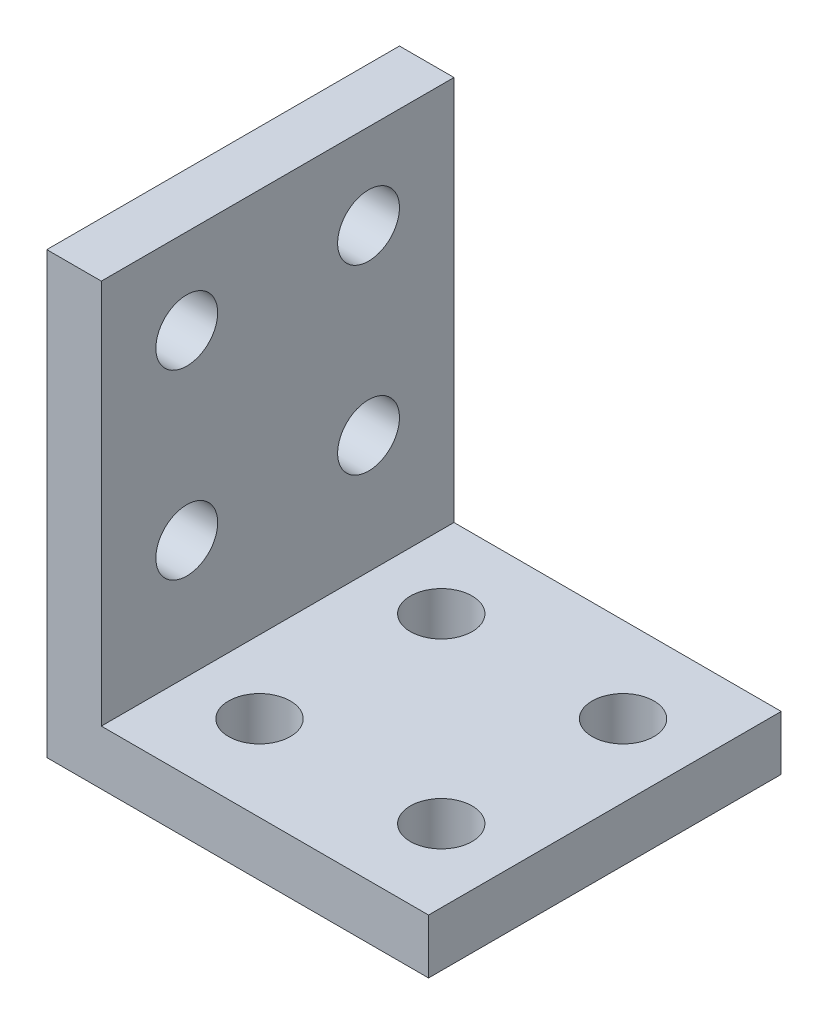
SolidWorks part; units mm, degrees
ref_plane "Front Plane" through (0, 0, 0) normal (0, 0, 1) x (1, 0, 0)
ref_plane "Top Plane" through (0, 0, 0) normal (0, 1, 0) x (1, 0, 0)
ref_plane "Right Plane" through (0, 0, 0) normal (1, 0, 0) x (0, 0, -1)
sketch "Sketch1" plane through (0, 0, 0) normal (0, 0, 1) x (1, 0, 0)
  line L0 (0, 24.2) -> (0, 0)
  line L1 (0, 0) -> (21, 0)
  line L2 (21, 0) -> (21, 3)
  line L3 (21, 3) -> (3, 3)
  line L4 (3, 3) -> (3, 24.2)
  line L5 (3, 24.2) -> (0, 24.2)
  dimension "D1" = 3
  dimension "D2" = 18
  dimension "D3" = 21.2
extrude "Boss-Extrude1" add sketch "Sketch1" along normal blind 19.4
hole_wizard "M3 Clearance Hole1" positions "Sketch8" profile "Sketch3" hole size "M3" standard "ANSI Metric" end condition through all
sketch "Sketch8" plane through (0, 3, 0) normal (0, 1, 0) x (1, 0, 0)
  line L0 (3, -9.7) -> (21, -9.7) construction
  line L1 (3, -19.4) -> (3, 0) construction
  line L2 (21, -19.4) -> (21, 0) construction
  line L4 (12, 0) -> (12, -19.4) construction
  line L5 (21, 0) -> (3, 0) construction
  line L6 (21, -19.4) -> (3, -19.4) construction
  line L7 (7, -14.7) -> (17, -14.7) construction
  line L8 (17, -14.7) -> (17, -4.7) construction
  line L9 (17, -4.7) -> (7, -4.7) construction
  line L10 (7, -4.7) -> (7, -14.7) construction
  point P15 (7, -4.7)
  point P17 (17, -4.7)
  point P19 (17, -14.7)
  point P21 (7, -14.7)
  point P32 (17, -9.7)
  point P35 (12, -4.7)
  dimension "D1" = 10
sketch "Sketch3" plane through (7, 3, 14.7) normal (1, 0, 0) x (0, 0, 1)
  line L0 (0, 0) -> (0, 3)
  line L1 (0, 3) -> (1.7, 3)
  line L2 (1.7, 3) -> (1.7, 0)
  line L5 (1.7, 0) -> (0, 0)
  line L11 (0, -6.35) -> (0, 107.95) construction
  dimension "Thru Hole Dia." = 3.4
  dimension "Thru Hole Depth" = 3
hole_wizard "M3 Clearance Hole2" positions "Sketch7" profile "Sketch5" hole size "M3" standard "ANSI Metric" end condition through all
sketch "Sketch7" plane through (3, 0, 0) normal (1, 0, 0) x (0, 0, -1)
  line L0 (-14.7, 9.5) -> (-14.7, 19.5) construction
  line L1 (-14.7, 19.5) -> (-4.7, 19.5) construction
  line L2 (-4.7, 19.5) -> (-4.7, 9.5) construction
  line L3 (-4.7, 9.5) -> (-14.7, 9.5) construction
  line L5 (-9.7, 3) -> (-9.7, 24.2) construction
  line L6 (-19.4, 24.2) -> (0, 24.2) construction
  line L12 (-19.4, 3) -> (0, 3) construction
  point P0 (-14.7, 9.5)
  point P2 (-4.7, 9.5)
  point P4 (-4.7, 19.5)
  point P6 (-14.7, 19.5)
  point P30 (-9.7, 9.5)
  dimension "D1" = 10
  dimension "D2" = 6.5
sketch "Sketch5" plane through (3, 9.5, 14.7) normal (0, 1, 0) x (0, 0, -1)
  line L0 (0, 0) -> (0, 3)
  line L1 (0, 3) -> (1.7, 3)
  line L2 (1.7, 3) -> (1.7, 0)
  line L5 (1.7, 0) -> (0, 0)
  line L11 (0, -6.35) -> (0, 107.95) construction
  dimension "Thru Hole Dia." = 3.4
  dimension "Thru Hole Depth" = 3
